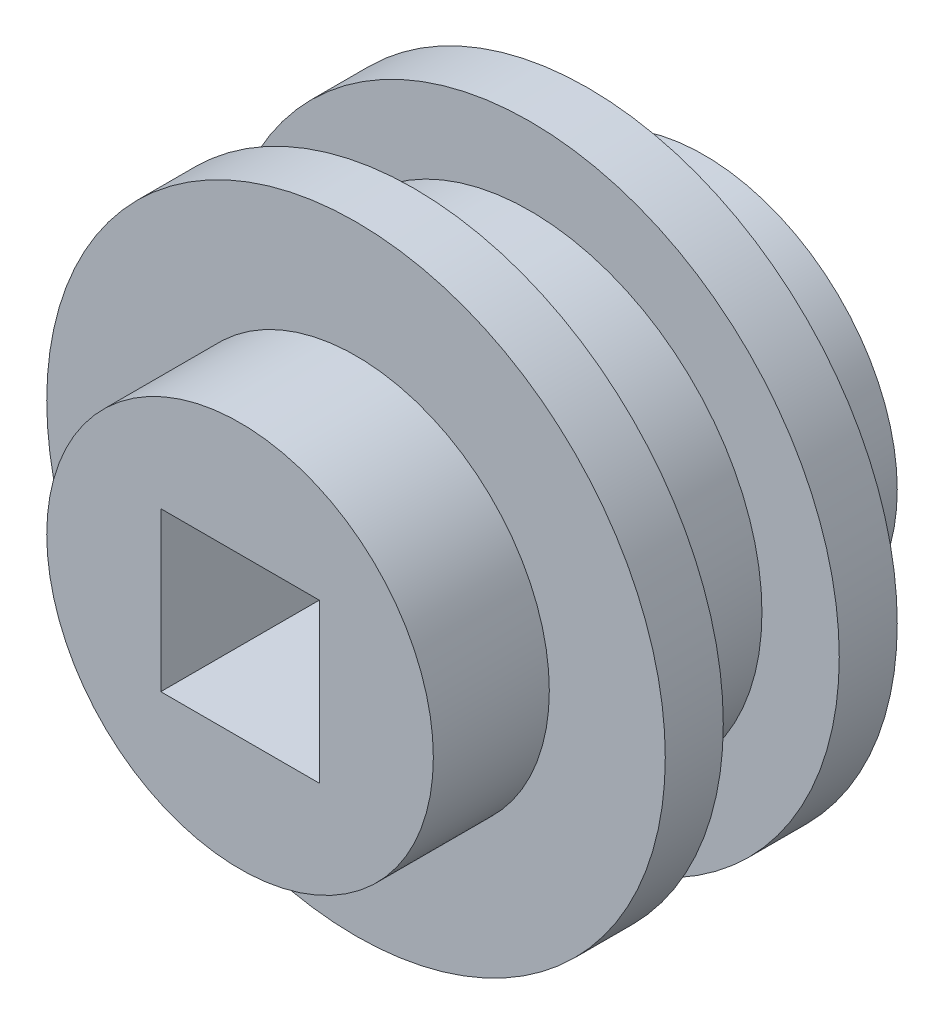
SolidWorks part; units mm, degrees
ref_plane "Front Plane" through (0, 0, 0) normal (0, 0, 1) x (1, 0, 0)
ref_plane "Top Plane" through (0, 0, 0) normal (0, 1, 0) x (1, 0, 0)
ref_plane "Right Plane" through (0, 0, 0) normal (1, 0, 0) x (0, 0, -1)
sketch "Sketch1" plane through (0, 0, 0) normal (0, 0, 1) x (1, 0, 0)
  line L1 (-2.05, -2.05) -> (2.05, -2.05)
  line L2 (-2.05, -2.05) -> (-2.05, 2.05)
  line L3 (-2.05, 2.05) -> (2.05, 2.05)
  line L4 (2.05, -2.05) -> (2.05, 2.05)
  line L5 (-2.05, -2.05) -> (2.05, 2.05) construction
  line L6 (-2.05, 2.05) -> (2.05, -2.05) construction
  circle A0 centre (0, 0) radius 5
  circle A1 centre (0, 0) radius 8
  dimension "D1" = 10
  dimension "D2" = 4.1
  dimension "D3" = 16
extrude "Boss-Extrude1" add sketch "Sketch1" along normal mid plane 12 contours A0 L4 L1 L2 L3 region at (-4.8586, 0, 0)
extrude "Boss-Extrude2" add sketch "Sketch1<3>" along normal mid plane 6 contours A1 A0 | A0 region at (-7.7737, 0, 0)
sketch "Sketch1<3>" plane through (0, 0, 0) normal (0, 0, 1) x (1, 0, 0) same geometry as "Sketch1"
extrude "Cut-Extrude-Thin1" cut sketch "Sketch1<6>" along normal mid plane 3 thin contours A1 thin type one direction reverse wall 2
sketch "Sketch1<6>" plane through (0, 0, 0) normal (0, 0, 1) x (1, 0, 0) same geometry as "Sketch1"
